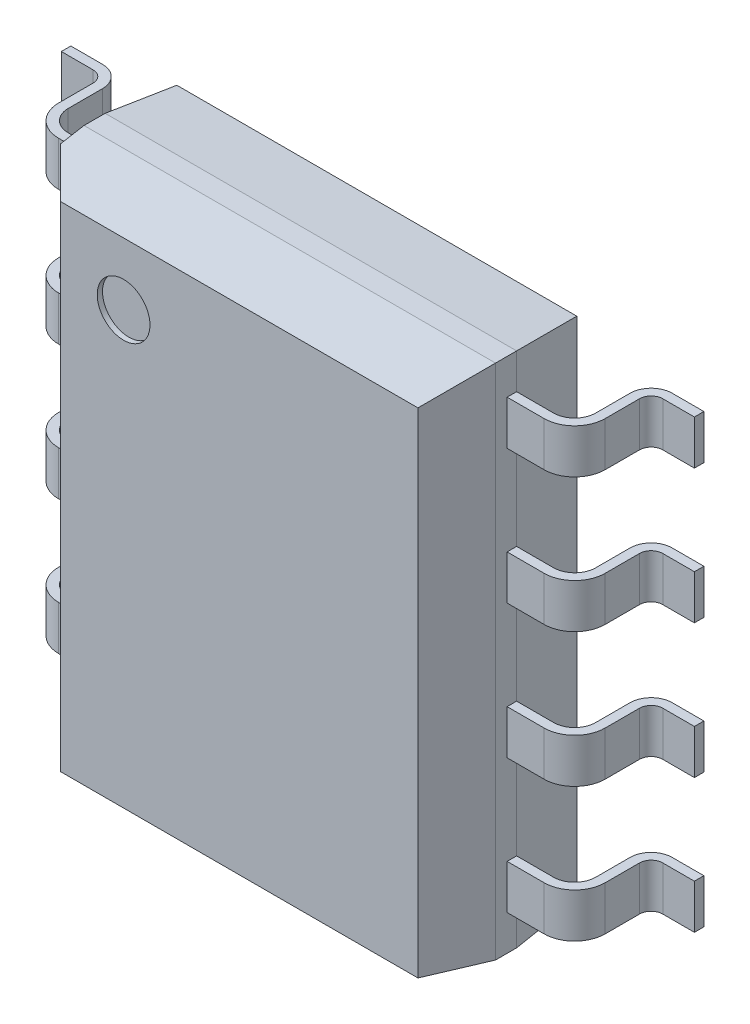
SolidWorks part; units mm, degrees
ref_plane "Face" through (0, 0, 0) normal (0, 0, 1) x (1, 0, 0)
ref_plane "Dessus" through (0, 0, 0) normal (0, 1, 0) x (1, 0, 0)
ref_plane "Droite" through (0, 0, 0) normal (1, 0, 0) x (0, 0, -1)
ref_plane "fond circuit" through (0, 0, 0.1) normal (0, 0, 1) x (1, 0, 0)
sketch "Esquisse2" plane through (0, 0, 0.1) normal (0, 0, 1) x (1, 0, 0)
  line L1 (-1.95, 2.45) -> (1.95, 2.45)
  line L2 (-1.95, 2.45) -> (-1.95, -2.45)
  line L3 (-1.95, -2.45) -> (1.95, -2.45)
  line L4 (1.95, 2.45) -> (1.95, -2.45)
  point P4 (1.95, 0)
  point P6 (0, 2.45)
  dimension "D1" = 3.9
  dimension "D2" = 4.9
extrude "corp" add sketch "Esquisse2" along normal blind 1.45
ref_plane "plan pin 1" through (0, 1.905, 0) normal (0, 1, 0) x (-1, 0, 0)
sketch "Esquisse6" plane through (0, 1.905, 0) normal (0, 1, 0) x (-1, 0, 0)
  line L0 (0, 0) -> (6.8831, 0) construction
  line L1 (1.95, 0.725) -> (2.3, 0.725)
  line L2 (1.95, 1.55) -> (1.95, 0.1) construction
  line L3 (2.5, 0.525) -> (2.5, 0.2)
  line L4 (3, 0) -> (2.7, 0)
  line L6 (-1.95, 1.55) -> (1.95, 1.55) construction
  arc A0 (2.3, 0.725) -> (2.5, 0.525) centre (2.3, 0.525) cw
  arc A1 (2.7, 0) -> (2.5, 0.2) centre (2.7, 0.2) cw
  dimension "D1" = 0.2
  dimension "D2" = 0.5
  dimension "D3" = 1.05
  dimension "D4" = 0.825
extrude "pin 1" add sketch "Esquisse6" along normal mid plane 0.42 thin thin type one direction wall 0.09
pattern_linear "Répétition pin 1-4" count 4 spacing 1.27 along (0, -1, 0) of "pin 1"
mirror "Symétrie1" about plane through (0, 0, 0) normal (1, 0, 0) of "Répétition pin 1-4"
ref_plane "Plan2" through (3.75, 0, 0) normal (1, 0, 0) x (0, 0, -1)
chamfer "Chanfrein4" distance 0.625 angle 10 3 edges at (0, 2.45, 1.55) (1.95, 0, 1.55) (0, -2.45, 1.55) first distance on face at (0, 2.45, 0.825) first distance on face at (1.95, -1.905, 0.77) first distance on face at (0, -2.45, 0.825)
chamfer "Chanfrein5" distance 0.625 angle 5 4 edges at (0, -2.45, 0.1) (1.95, 0, 0.1) (0, 2.45, 0.1) (-1.95, 0, 0.1) first distance on face at (0, -2.45, 0.5125) first distance on face at (1.95, -1.905, 0.77) first distance on face at (0, 2.45, 0.5125) first distance on face at (-1.95, -1.905, 0.77)
sketch "Esquisse8" plane through (0, 0, 1.55) normal (0, 0, 1) x (1, 0, 0)
  line L0 (-1.95, 2.45) -> (-1.95, 2.115) construction
  line L3 (-1.95, 2.45) -> (1.95, 2.45) construction
  circle A0 centre (-0.95, 1.75) radius 0.25
  dimension "D1" = 0.5
  dimension "D2" = 1
  dimension "D3" = 0.7
extrude "Enlèv. mat.-Extru.1" cut sketch "Esquisse8" against normal blind 0.05
chamfer "Chanfrein7" distance 0.4 angle 45 1 edges at (-1.95, 0, 1.55)
